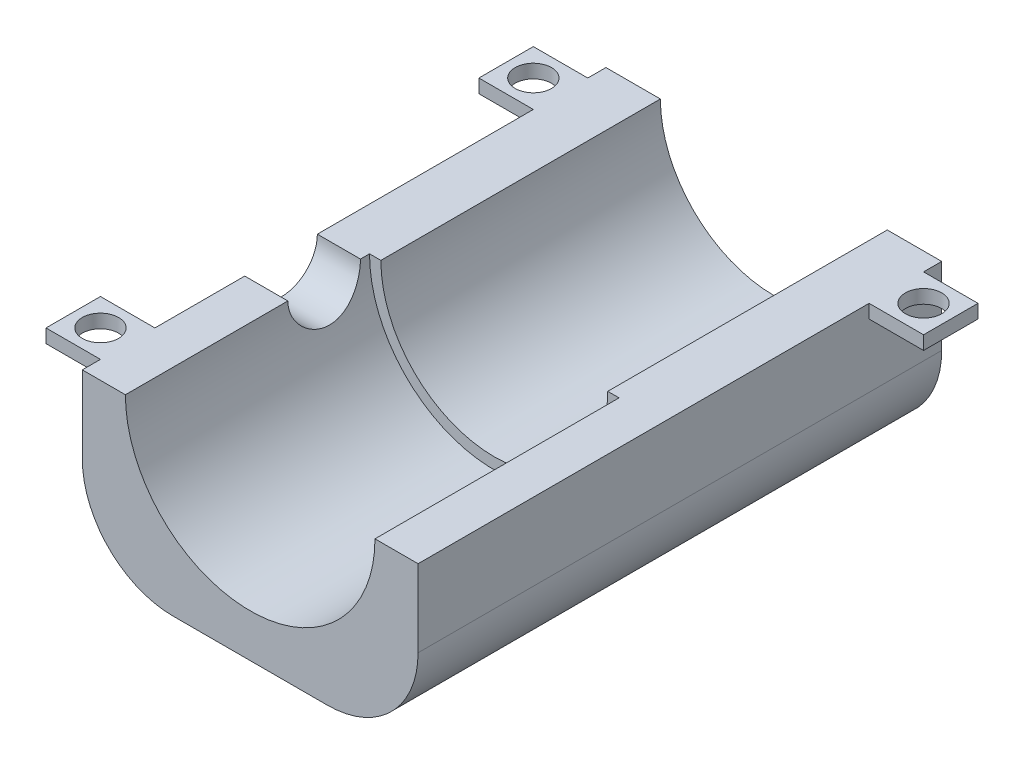
SolidWorks part; units mm, degrees
ref_plane "정면도" through (0, 0, 0) normal (0, 0, 1) x (1, 0, 0)
ref_plane "평면도" through (0, 0, 0) normal (0, 1, 0) x (1, 0, 0)
ref_plane "우측면도" through (0, 0, 0) normal (1, 0, 0) x (0, 0, -1)
sketch "스케치1" plane through (0, 0, 0) normal (0, 0, 1) x (1, 0, 0)
  line L0 (-13.5, 0) -> (-18.5, 0)
  line L1 (-18.5, 0) -> (-18.5, -18.5)
  line L2 (-18.5, -18.5) -> (18.5, -18.5)
  line L3 (18.5, -18.5) -> (18.5, 0)
  line L4 (18.5, 0) -> (13.5, 0)
  arc A0 (-13.5, 0) -> (13.5, 0) centre (0, 0) ccw
  arc A1 (-16, 0) -> (16, 0) centre (0, 0) ccw construction
  circle A2 centre (0, 0) radius 11.5
  point P9 (0, -16)
  dimension "D1" = 27
  dimension "D2" = 32
  dimension "D6" = 23
  dimension "D3" = 5
  dimension "D4" = 5
  dimension "D5" = 2.5
extrude "보스-돌출1" add sketch "스케치1" against normal blind 57.7 contours L1 L2 L3 L4 A0 L0
ref_plane "평면1" through (0, 0, -26.9) normal (0, 0, 1) x (1, 0, 0)
sketch "스케치3" plane through (0, 0, -26.9) normal (0, 0, 1) x (1, 0, 0)
  line L0 (-13.5, 0) -> (-11.5, 0)
  line L1 (13.5, 0) -> (11.5, 0)
  circle A0 centre (0, 0) radius 11.5 construction
  arc A1 (-11.5, 0) -> (11.5, 0) centre (0, 0) ccw
  arc A2 (-13.5, 0) -> (13.5, 0) centre (0, 0) ccw construction
  arc A3 (-13.5, 0) -> (13.5, 0) centre (0, 0) ccw
extrude "보스-돌출2" add sketch "스케치3" against normal blind 30.8
sketch "스케치5" plane through (-18.5, 0, 0) normal (-1, 0, 0) x (0, 0, 1)
  line L0 (-57.7, 0) -> (0, 0) construction
  line L1 (0, 0) -> (0, -18.5) construction
  circle A0 centre (-21.9, 0) radius 4
  dimension "D2" = 8
  dimension "D1" = 21.9
extrude "컷-돌출1" cut sketch "스케치5" against normal blind 15
fillet "필렛1" radius 10 2 edges at (-18.5, -18.5, -28.85) (18.5, -18.5, -28.85)
sketch "스케치6" plane through (18.5, 0, 0) normal (1, 0, 0) x (0, 0, -1)
  line L0 (57.7, 0) -> (0, 0) construction
  line L1 (2, 1.5) -> (8, 1.5)
  line L2 (2, 1.5) -> (2, -1.5)
  line L3 (2, -1.5) -> (8, -1.5)
  line L4 (8, 1.5) -> (8, -1.5)
  line L5 (5, -1.5) -> (5, 1.5) construction
  line L6 (2, 0) -> (8, 0) construction
  line L7 (0, -8.5) -> (0, 0) construction
  line L8 (55.7, 1.5) -> (49.7, 1.5)
  line L9 (55.7, 1.5) -> (55.7, -1.5)
  line L10 (55.7, -1.5) -> (49.7, -1.5)
  line L11 (49.7, 1.5) -> (49.7, -1.5)
  line L12 (52.7, -1.5) -> (52.7, 1.5) construction
  line L13 (55.7, 0) -> (49.7, 0) construction
  line L14 (57.7, -8.5) -> (57.7, 0) construction
  line L15 (55.7, 0) -> (49.7, 0)
  line L16 (8, 0) -> (2, 0)
  point P0 (5, 0)
  point P6 (52.7, 0)
  line M8 (57.7, 0) -> (0, 0)
  dimension "D1" = 5
  dimension "D2" = 3
  dimension "D3" = 6
  dimension "D4" = 5
  dimension "D5" = 6
  dimension "D6" = 3
extrude "보스-돌출3" add sketch "스케치6" along normal blind 6 contours L11 L10 L9 M8 | L4 L2 L3 M8 region at (18.5, -0.75, -52.7) region at (18.5, -0.75, -5)
extrude "보스-돌출4" add sketch "스케치6<3>" against normal blind 6 from surface contours L11 L10 L9 M8 | L4 L2 L3 M8 region at (18.5, -0.75, -52.7) region at (18.5, -0.75, -5) starting at face at (-18.5, -3.5, -26.5333)
sketch "스케치6<3>" plane through (18.5, 0, 0) normal (1, 0, 0) x (0, 0, -1) same geometry as "스케치6"
sketch "스케치7" plane through (0, 0, 0) normal (0, 1, 0) x (1, 0, 0)
  line L0 (0, 0) -> (0, 57.7) construction
  line L1 (11.5, 57.7) -> (-11.5, 57.7) construction
  line L2 (18.5, 8) -> (24.5, 2) construction
  line L3 (18.5, 2) -> (18.5, 8) construction
  line L4 (24.5, 8) -> (18.5, 8) construction
  line L5 (24.5, 8) -> (18.5, 2) construction
  line L6 (18.5, 55.7) -> (24.5, 49.7) construction
  line L7 (18.5, 49.7) -> (24.5, 55.7) construction
  circle A0 centre (21.5, 5) radius 2
  circle A1 centre (21.5, 52.7) radius 2
  circle A2 centre (-21.5, 5) radius 2
  circle A3 centre (-21.5, 52.7) radius 2
  dimension "D1" = 4
extrude "컷-돌출2" cut sketch "스케치7" against normal blind 6
sketch "스케치8" plane through (0, -18.5, 0) normal (0, -1, 0) x (1, 0, 0)
  line L0 (8.5, -57.7) -> (8.5, 0) construction
  line L1 (7.25, -30.2) -> (-7.25, -30.2)
  line L2 (7.25, -30.2) -> (7.25, -55.7)
  line L3 (7.25, -55.7) -> (-7.25, -55.7)
  line L4 (-7.25, -30.2) -> (-7.25, -55.7)
  line L5 (-8.5, -57.7) -> (8.5, -57.7) construction
  dimension "D1" = 14.5
  dimension "D2" = 25.5
  dimension "D3" = 1.25
  dimension "D4" = 2
extrude "컷-돌출3" cut sketch "스케치8" against normal blind 2
sketch "스케치9" plane through (0, 0, 0) normal (0, 0, 1) x (1, 0, 0)
  line L0 (-13.5, 0) -> (-13.75, 0)
  line L1 (13.5, 0) -> (13.75, 0)
  arc A0 (-13.75, 0) -> (13.75, 0) centre (0, 0) ccw
  arc A1 (-13.5, 0) -> (13.5, 0) centre (0, 0) ccw construction
  arc A2 (-13.5, 0) -> (13.5, 0) centre (0, 0) ccw
  dimension "D1" = 0.25
extrude "컷-돌출4" cut sketch "스케치9" against normal up to surface (26.9 mm away) up to face at (0, -6.25, -26.9)
sketch "스케치10" plane through (0, 0, -26.9) normal (0, 0, 1) x (1, 0, 0)
  line L2 (-11.5, 0) -> (-13.75, 0) construction
  line L3 (13.75, 0) -> (11.5, 0) construction
  line L4 (-11.5, 0) -> (-12.5, 0)
  line L5 (13.75, 0) -> (11.5, 0)
  arc A3 (-12.5, 0) -> (12.5, 0) centre (0, 0) ccw
  arc A4 (-11.5, 0) -> (11.5, 0) centre (0, 0) ccw construction
  arc A5 (-11.5, 0) -> (11.5, 0) centre (0, 0) ccw
  line M2 (-11.5, 0) -> (-13.75, 0)
  arc M5 (11.5, 0) -> (-11.5, 0) centre (0, 0) cw
  dimension "D1" = 25
extrude "컷-돌출5" cut sketch "스케치10" against normal through all contours A3 L5 M2 M5 | A3 L4 A5 L5 region at (0, -11.7795, -26.9)
sketch "스케치11" plane through (0, -1.5, 0) normal (0, -1, 0) x (1, 0, 0)
  line L1 (24.5, -8) -> (18.5, -8)
  line L2 (24.5, -8) -> (24.5, -2)
  line L3 (24.5, -2) -> (18.5, -2)
  line L4 (18.5, -8) -> (18.5, -2)
extrude "컷-돌출6" cut sketch "스케치11" against normal blind 10
